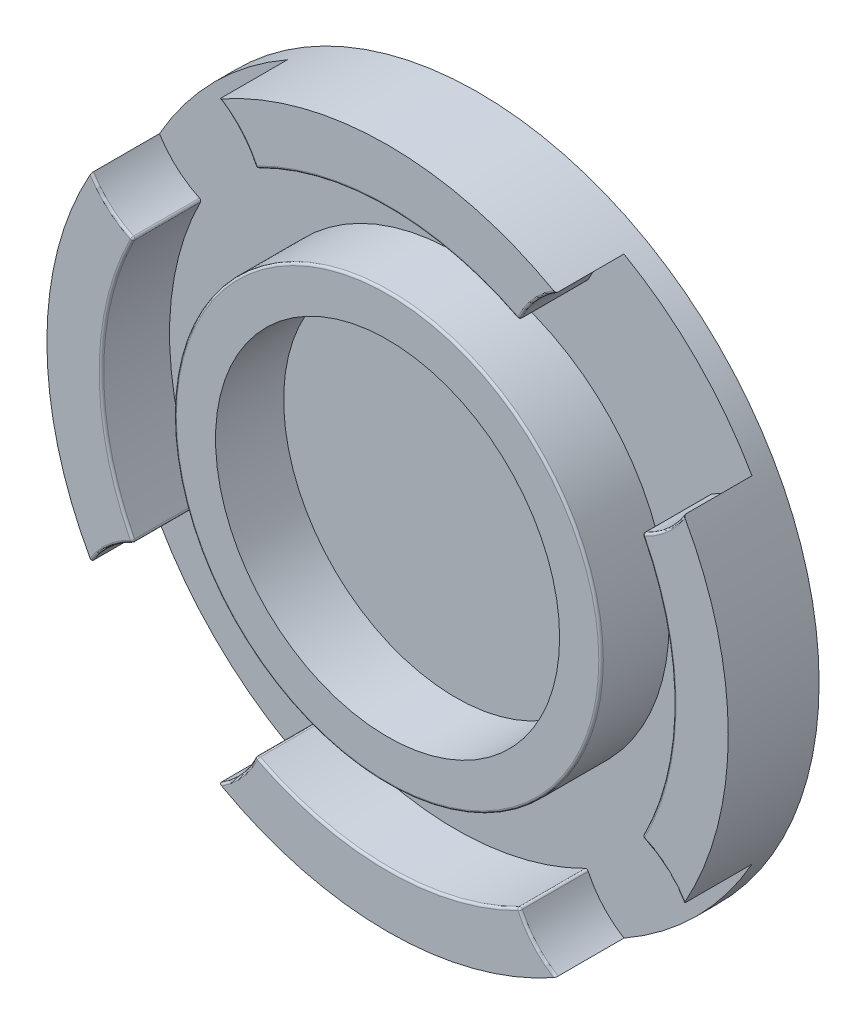
SolidWorks part; units mm, degrees
ref_plane "Front Plane" through (0, 0, 0) normal (0, 0, 1) x (1, 0, 0)
ref_plane "Top Plane" through (0, 0, 0) normal (0, 1, 0) x (1, 0, 0)
ref_plane "Right Plane" through (0, 0, 0) normal (1, 0, 0) x (0, 0, -1)
sketch "Sketch1" plane through (0, 0, 0) normal (0, 0, 1) x (1, 0, 0)
  line L0 (0, 0) -> (13.5, 0) construction
  line L1 (0, 0) -> (9.5459, 9.5459) construction
  circle A0 centre (0, 0) radius 9.4
  circle A1 centre (0, 0) radius 15
  arc A2 (-6.2402, 11.9712) -> (-11.9712, 6.2402) centre (0, 0) ccw construction
  arc A3 (7.4069, 13.0437) -> (5.7903, 11.1907) centre (9.5459, 9.5459) ccw
  arc A4 (13.0437, -7.4069) -> (11.1907, -5.7903) centre (9.5459, -9.5459) ccw
  arc A5 (-7.4069, -13.0437) -> (-5.7903, -11.1907) centre (-9.5459, -9.5459) ccw
  arc A6 (-13.0437, 7.4069) -> (-11.1907, 5.7903) centre (-9.5459, 9.5459) ccw
  arc A7 (-11.1907, 5.7903) -> (-11.1907, -5.7903) centre (0, 0) ccw
  arc A8 (11.9712, 6.2402) -> (6.2402, 11.9712) centre (0, 0) ccw construction
  arc A9 (6.2402, -11.9712) -> (11.9712, -6.2402) centre (0, 0) ccw construction
  arc A10 (-11.9712, -6.2402) -> (-6.2402, -11.9712) centre (0, 0) ccw construction
  arc A11 (5.7903, 11.1907) -> (-5.7903, 11.1907) centre (0, 0) ccw
  arc A12 (-5.7903, -11.1907) -> (5.7903, -11.1907) centre (0, 0) ccw
  arc A13 (11.1907, -5.7903) -> (11.1907, 5.7903) centre (0, 0) ccw
  arc A14 (-5.7903, 11.1907) -> (-7.4069, 13.0437) centre (-9.5459, 9.5459) ccw
  arc A15 (11.1907, 5.7903) -> (13.0437, 7.4069) centre (9.5459, 9.5459) ccw
  arc A16 (5.7903, -11.1907) -> (7.4069, -13.0437) centre (9.5459, -9.5459) ccw
  arc A17 (-11.1907, -5.7903) -> (-13.0437, -7.4069) centre (-9.5459, -9.5459) ccw
  circle A18 centre (0, 0) radius 7.575
  point P17 (0, 0)
  dimension "D1" = 18.8
  dimension "D2" = 30
  dimension "D3" = 27
  dimension "D4" = 45
  dimension "D5" = 8.2
  dimension "D6" = 4
  dimension "D7" = 25.2
  dimension "D8" = 15.15
extrude "Boss-Extrude1" add sketch "Sketch1" along normal blind 3 contours A14 A11 A3 A1 | A15 A13 A4 A1 | A16 A12 A5 A1 | A17 A7 A6 A1 | A0 A18 region at (-9.1341, 0, 0) region at (13.3026, 0, 0) region at (0, 13.3026, 0) region at (0, -13.3026, 0) region at (-13.3026, 0, 0)
sketch "Sketch2" plane through (0, 0, 0) normal (0, 0, 1) x (1, 0, 0)
  circle A0 centre (0, 0) radius 15
extrude "Boss-Extrude2" add sketch "Sketch2" against normal blind 1
fillet "Fillet1" radius 0.1 8 edges at (-5.7903, -11.1907, 1.5) (5.7903, -11.1907, 1.5) (11.1907, -5.7903, 1.5) (11.1907, 5.7903, 1.5) (5.7903, 11.1907, 1.5) (-5.7903, 11.1907, 1.5) (-11.1907, 5.7903, 1.5) (-11.1907, -5.7903, 1.5)
fillet "Fillet2" radius 0.1 21 edges at (6.4907, 12.2801, 3) (5.7751, 11.233, 3) (-6.4907, 12.2801, 3) (-5.7751, 11.233, 3) (12.2801, -6.4907, 3) (11.233, -5.7751, 3) (12.2801, 6.4907, 3) (11.233, 5.7751, 3) (-6.4907, -12.2801, 3) (-5.7751, -11.233, 3) (6.4907, -12.2801, 3) (5.7751, -11.233, 3) (-12.2801, 6.4907, 3) (-11.233, 5.7751, 3) (-12.2801, -6.4907, 3) (-11.233, -5.7751, 3) (0, 12.6, 3) (12.6, 0, 3) (0, -12.6, 3) (9.4, 0, 3) (-12.6, 0, 3)
